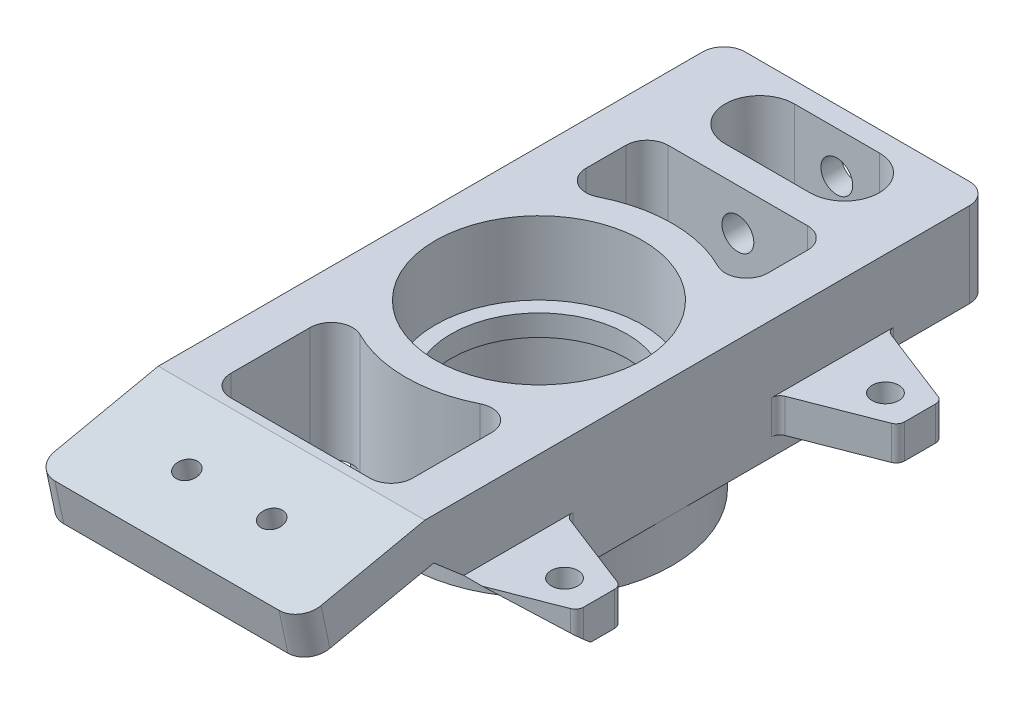
SolidWorks part; units mm, degrees
material "6061-T6 (SS)"
ref_plane "Front Plane" through (0, 0, 0) normal (0, 0, 1) x (1, 0, 0)
ref_plane "Top Plane" through (0, 0, 0) normal (0, 1, 0) x (1, 0, 0)
ref_plane "Right Plane" through (0, 0, 0) normal (1, 0, 0) x (0, 0, -1)
sketch "Geometry" plane through (0, 0, 0) normal (1, 0, 0) x (0, 0, -1)
  line L0 (0, 0) -> (0, -97.4059) construction
  line L1 (0, 0) -> (-30.7529, 0) construction
  line L2 (0, 22) -> (-45.5659, 22) construction
  dimension "D1" = 22
sketch "Sketch1" plane through (0, 0, 0) normal (0, 0, 1) x (1, 0, 0)
  line L1 (0, 0) -> (0, -13.28) construction
  line L3 (-30.9994, -10.5425) -> (-30.9994, -32.3865)
  line L4 (-30.9994, -32.3865) -> (-26.289, -32.3865)
  line L5 (-26.289, -32.3865) -> (-26.289, -38.7365)
  line L6 (-26.289, -38.7365) -> (-30.9994, -38.7365)
  line L7 (-30.9994, -38.7365) -> (-30.9994, -63.1205)
  line L8 (-30.9994, -63.1205) -> (-32.258, -63.1205)
  line L9 (-32.258, -63.1205) -> (-32.258, -59.3105)
  line L10 (-32.258, -59.3105) -> (-39.878, -59.3105)
  line L11 (-39.878, -59.3105) -> (-39.878, -10.5425)
  line L12 (-39.878, -10.5425) -> (-30.9994, -10.5425)
  line L13 (-80.1186, -10.5425) -> (80.1186, -10.5425) construction
  dimension "D1" = 6.35
  dimension "D2" = 21.844
  dimension "D3" = 24.384
  dimension "D4" = 52.578
  dimension "D5" = 61.9989
  dimension "D6" = 64.516
  dimension "D7" = 79.756
  dimension "D8" = 48.768
revolve "Bearing Housing" add sketch "Sketch1" angle 360 about L1
fillet "Bearing Fillet" radius 6.35 1 edges at (-32.258, -59.3105, 0)
sketch "Sketch2" plane through (0, -10.5425, 0) normal (0, -1, 0) x (-1, 0, 0)
  line L0 (-39.878, 50.8) -> (-39.878, 0)
  line L1 (39.878, 50.8) -> (39.878, 0)
  line L2 (-39.878, 50.8) -> (39.878, 50.8)
  circle A0 centre (0, 0) radius 39.878 construction
  arc A1 (-39.878, 0) -> (39.878, 0) centre (0, 0) cw
  dimension "D1" = 50.8
extrude "LBJ Prep" add sketch "Sketch2" along normal blind 35.56
sketch "Sketch3" plane through (-39.878, 0, 0) normal (-1, 0, 0) x (0, 0, 1)
  line L0 (-50.8, -10.5425) -> (-95.1865, -10.5425)
  line L1 (-95.1865, -10.5425) -> (-95.1865, -35.9425)
  line L2 (-95.1865, -35.9425) -> (-58.42, -35.9425)
  line L3 (-58.42, -35.9425) -> (-50.8, -46.1025)
  line L4 (-50.8, -46.1025) -> (-50.8, -10.5425)
  circle A1 centre (-78.74, -23.2425) radius 10.3505 construction
  dimension "D3" = 25.4
  dimension "D4" = 20.701
  dimension "D2" = 7.62
  dimension "D1" = 78.74
  dimension "D5" = 12.7
  dimension "D6" = 6.096
extrude "LBJ Extrude" add sketch "Sketch3" against normal up to surface (79.756 mm away) up to face at (39.878, -28.3225, -25.4)
sketch "Sketch4" plane through (0, -35.9425, 0) normal (0, -1, 0) x (1, 0, 0)
  line L0 (-12.7, -78.74) -> (12.7, -78.74) construction
  line L1 (0, -200000) -> (0, 200052.2037) construction
  line L2 (-12.7, -68.3895) -> (12.7, -68.3895)
  line L3 (-12.7, -89.0905) -> (12.7, -89.0905)
  arc A0 (-12.7, -68.3895) -> (-12.7, -89.0905) centre (-12.7, -78.74) ccw
  arc A1 (12.7, -89.0905) -> (12.7, -68.3895) centre (12.7, -78.74) ccw
  point P4 (0, -78.74)
  dimension "D1" = 20.701
  dimension "D2" = 78.74
  dimension "D3" = 25.4
extrude "LBJ Slot" cut sketch "Sketch4" against normal through all
sketch "Sketch8" plane through (0, -46.1025, 0) normal (0, -1, 0) x (1, 0, 0)
  line L0 (-27.178, -29.1824) -> (-27.178, -59.4995)
  line L1 (-27.178, -59.4995) -> (27.178, -59.4995)
  line L2 (27.178, -59.4995) -> (27.178, -29.1824)
  line L3 (-39.878, 0) -> (-39.878, -50.8) construction
  line L4 (39.878, -50.8) -> (39.878, 0) construction
  line L5 (12.7, -68.3895) -> (-12.7, -68.3895) construction
  arc A0 (-39.878, 0) -> (39.878, 0) centre (0, 0) ccw construction
  arc A1 (-27.178, -29.1824) -> (27.178, -29.1824) centre (0, 0) ccw
  dimension "D1" = 12.7
  dimension "D2" = 12.7
  dimension "D3" = 8.89
extrude "LBJ Weight Saivng" cut sketch "Sketch8" against normal up to surface (35.56 mm away)
fillet "LBJ Fillet" radius 6.35 4 edges at (-27.178, -23.2425, -59.4995) (27.178, -23.2425, -59.4995) (27.178, -28.3225, -29.1824) (-27.178, -28.3225, -29.1824)
sketch "Sketch12" plane through (0, 0, -95.1865) normal (0, 0, -1) x (-1, 0, 0)
  line L0 (0, 200000) -> (0, -200097.4059) construction
  circle A0 centre (0, -22.958) radius 4.7625
  dimension "D1" = 9.525
  dimension "D2" = 22.958
extrude "LBJ Hole" cut sketch "Sketch12" against normal up to surface (35.687 mm away) up to face at (0, -23.2425, -59.4995)
sketch "Alignment for LBJ Clearance" plane through (0, 0, -95.1865) normal (0, 0, -1) x (-1, 0, 0)
  line L0 (0, -22.958) -> (8.6177, -33.2282) construction
  line L1 (0, 200000) -> (0, -200097.4059) construction
  circle A1 centre (0, -22.958) radius 12.7 construction
  circle A2 centre (0, -22.958) radius 4.7625 construction
  dimension "D1" = 25.4
  dimension "D2" = 40
ref_plane "Plane1" through (0, -22.958, -95.1865) normal (-0.6428, -0.766, 0) x (-0.766, 0.6428, 0)
sketch "Sketch17" plane through (0, -22.958, -95.1865) normal (-0.6428, -0.766, 0) x (-0.766, 0.6428, 0)
  line L0 (0, -6.096) -> (0, -26.797) construction
  line L1 (4.7625, -26.797) -> (-4.7625, -26.797) construction
  line L3 (-4.7625, -6.096) -> (4.7625, -6.096) construction
  line L7 (4.7625, -26.797) -> (-4.7625, -26.797) construction
  line L8 (-1.27, -16.4465) -> (1.27, -16.4465) construction
  line L9 (-1.27, -6.096) -> (1.27, -6.096)
  line L10 (-1.27, -26.797) -> (1.27, -26.797)
  arc A2 (-1.27, -6.096) -> (-1.27, -26.797) centre (-1.27, -16.4465) ccw
  arc A3 (1.27, -26.797) -> (1.27, -6.096) centre (1.27, -16.4465) ccw
  point P7 (0, -16.4465)
  dimension "D1" = 2.54
  dimension "D2" = 20.701
extrude "LBJ Widening" cut sketch "Sketch17" along normal through all
mirror "LBJ Widening " about plane through (0, 0, 0) normal (1, 0, 0) of "LBJ Widening"
sketch "Sketch5" plane through (0, -10.5425, 0) normal (0, -1, 0) x (-1, 0, 0)
  line L0 (-39.878, -44.45) -> (39.878, -44.45)
  line L1 (39.878, -44.45) -> (39.878, 0)
  line L2 (-39.878, -44.45) -> (-39.878, 0)
  circle A0 centre (0, 0) radius 39.878 construction
  arc A1 (-39.878, 0) -> (39.878, 0) centre (0, 0) ccw
  dimension "D1" = 44.45
extrude "UBJ Area Prep" add sketch "Sketch5" along normal blind 35.56
sketch "UBJ Angle " plane through (-39.878, 0, 0) normal (-1, 0, 0) x (0, 0, 1)
  line L0 (44.45, -10.5425) -> (73.9986, -10.5425)
  line L1 (73.9986, -10.5425) -> (111.266, -18.4639)
  line L2 (111.266, -18.4639) -> (108.6256, -30.8864)
  line L3 (108.6256, -30.8864) -> (71.3581, -22.965)
  line L4 (71.3581, -22.965) -> (44.45, -46.1025)
  line L5 (44.45, -46.1025) -> (44.45, -10.5425)
  line L6 (92.6323, -14.5032) -> (69.5361, -123.1622) construction
  line L7 (71.3581, -22.965) -> (73.9986, -10.5425) construction
  line L8 (0, 0) -> (79.4354, 0) construction
  line L9 (44.45, -10.5425) -> (-95.1865, -10.5425) construction
  line L10 (-27.2547, 22) -> (21.0785, 22) construction
  line L11 (0, 0) -> (0, 33.0044) construction
  circle A0 centre (84.7344, -51.66) radius 10.3251 construction
  dimension "D8" = 20.6502
  dimension "D1" = 19.05
  dimension "D2" = 38.1
  dimension "D3" = 12.7
  dimension "D5" = 22
  dimension "D7" = 12
  dimension "D4" = 84.7344
  dimension "D6" = 73.66
extrude "UBJ Angle Mount" add sketch "UBJ Angle " against normal up to surface (79.756 mm away) up to face at (39.878, -33.0396, -30.099)
sketch "Sketch7" plane through (0, -7.4603, -1.5857) normal (0, -0.9781, -0.2079) x (1, 0, 0)
  line L0 (0, 112.6735) -> (0, 78.6798) construction
  line L2 (-12.7, 93.6235) -> (12.7, 93.6235) construction
  line L3 (39.878, 112.6735) -> (-39.878, 112.6735) construction
  circle A2 centre (-12.7, 93.6235) radius 3.2639
  circle A3 centre (12.7, 93.6235) radius 3.2639
  point P3 (0, 93.6235)
  dimension "D4" = 6.5278
  dimension "D1" = 25.4
  dimension "D2" = 19.05
extrude "Camber Block Holes" cut sketch "Sketch7" against normal up to surface (12.7 mm away) up to face at (0, -14.5032, 92.6323)
sketch "Sketch9" plane through (0, -46.1025, 0) normal (0, -1, 0) x (1, 0, 0)
  line L0 (-27.178, 29.1824) -> (-27.178, 71.3581)
  line L1 (-27.178, 71.3581) -> (27.178, 71.3581)
  line L2 (27.178, 71.3581) -> (27.178, 29.1824)
  line L4 (-39.878, 44.45) -> (-39.878, 0) construction
  line L5 (39.878, 0) -> (39.878, 44.45) construction
  line L6 (39.878, 71.3581) -> (-39.878, 71.3581) construction
  arc A3 (-27.178, 29.1824) -> (27.178, 29.1824) centre (0, 0) cw
  arc A4 (39.878, 0) -> (-39.878, 0) centre (0, 0) ccw construction
  dimension "D1" = 12.7
  dimension "D2" = 12.7
extrude "UBJ Weight Saving" cut sketch "Sketch9" against normal up to surface (35.56 mm away)
fillet "UBJ Fillets" radius 6.35 4 edges at (27.178, -28.3225, 29.1824) (-27.178, -28.3225, 29.1824) (27.178, -16.7537, 71.3581) (-27.178, -16.7537, 71.3581)
ref_plane "Brake Caliper Face " through (0, -30.7025, 0) normal (0, 1, 0) x (1, 0, 0)
sketch "Sketch13" plane through (0, -30.7025, 0) normal (0, 1, 0) x (1, 0, 0)
  line L0 (55.6468, 116.3651) -> (55.6468, 49.0638) construction
  line L1 (0, 0) -> (78.791, 0) construction
  line L2 (65.9968, -54.35) -> (65.9968, -41.65)
  line L3 (65.9968, -41.65) -> (39.878, -31.49)
  line L4 (39.878, -31.49) -> (39.878, -64.51)
  line L5 (39.878, -64.51) -> (65.9968, -54.35)
  line L6 (39.878, 95.1865) -> (39.878, -73.9986) construction
  line L7 (65.9968, -48) -> (55.6468, -48) construction
  line L8 (39.878, 31.49) -> (39.878, 64.51)
  line L9 (39.878, 64.51) -> (65.9968, 54.35)
  line L10 (65.9968, 54.35) -> (65.9968, 41.65)
  line L11 (65.9968, 41.65) -> (39.878, 31.49)
  circle A0 centre (55.6468, -48) radius 4
  circle A1 centre (55.6468, 48) radius 4
  dimension "D3" = 8
  dimension "D1" = 55.6468
  dimension "D2" = 96
  dimension "D4" = 6.35
  dimension "D5" = 33.02
  dimension "D6" = 12.7
extrude "Brake Arms" add sketch "Sketch13" against normal blind 10.16
sketch "Sketch15" plane through (39.878, 0, 0) normal (-1, 0, 0) x (0, 0, 1)
  line L0 (64.51, -28.8535) -> (50.5439, -40.8625)
  line L1 (44.45, -46.1025) -> (71.3581, -22.965) construction
  line L2 (50.5439, -40.8625) -> (64.51, -40.8625)
  line L3 (50.5439, -40.8625) -> (64.51, -40.8625) construction
  line L4 (64.51, -28.8535) -> (64.51, -40.8625)
  line L5 (64.51, -40.8625) -> (64.51, -30.7025) construction
extrude "Upper Brake Cut" cut sketch "Sketch15" against normal through all
sketch "Sketch16" plane through (39.878, 0, 0) normal (-1, 0, 0) x (0, 0, 1)
  line L0 (-58.42, -35.9425) -> (-95.1865, -35.9425)
  line L1 (-95.1865, -35.9425) -> (-58.42, -35.9425) construction
  line L2 (-95.1865, -35.9425) -> (-95.1865, -46.1025)
  line L3 (-95.1865, -46.1025) -> (-50.8, -46.1025)
  line L4 (-50.8, -46.1025) -> (-58.42, -35.9425)
  line L5 (-95.1865, -10.5425) -> (-95.1865, -35.9425) construction
extrude "Lower Brake Cut" cut sketch "Sketch16" against normal through all
fillet "Fillet1" radius 2.54 7 edges at (65.9968, -34.1461, 54.35) (65.9968, -35.7825, 41.65) (65.9968, -35.7825, -41.65) (65.9968, -35.7825, -54.35) (39.878, -33.3225, -64.51) (39.878, -35.7825, -31.49) (39.878, -35.7825, 31.49)
sketch "Sketch14" plane through (-39.878, 0, 0) normal (-1, 0, 0) x (0, 0, 1)
  line L0 (73.9986, -10.5425) -> (-95.1865, -10.5425) construction
  circle A0 centre (-31.242, -20.1945) radius 3.175
  circle A1 centre (-31.242, -37.4665) radius 3.175
  circle A2 centre (-55.118, -20.1945) radius 3.175
  dimension "D3" = 6.35
  dimension "D4" = 6.35
  dimension "D5" = 6.35
  dimension "D1" = 17.272
  dimension "D2" = 23.876
  dimension "D6" = 31.242
  dimension "D7" = 9.652
extrude "Tie Rod Mound" cut sketch "Sketch14" against normal blind 6.35
fillet "Fillet2" radius 6.35 4 edges at (-39.878, -23.2425, -95.1865) (39.878, -23.2425, -95.1865) (39.878, -24.6752, 109.9458) (-39.878, -24.6752, 109.9458)
equation "\"Wheel_Offset\"= 22mm"
equation "\"HUB_to_UBJ_Lat\"= 2.9in"
equation "\"Hub_to_UBJ_Vert\"= 3.336in"
equation "\"Hub_to_LBJ_Lat\"= 1.77in"
equation "\"Hub_to_LBJ_Vert\"= 3.1in"
equation "\"Wheel_face_to_Upright_back\"= 1.2812in'This is the distance between the whee face to the upright back."
equation "\"D2@Sketch4\"=\"Hub_to_LBJ_Vert\""
equation "\"D5@UBJ Angle \" = \"Wheel_Offset\""
equation "\"UBJ_Angle\"= 12deg"
equation "\"D7@UBJ Angle \" = \"UBJ_Angle\""
equation "\"D4@UBJ Angle \"=\"Hub_to_UBJ_Vert\""
equation "\"D6@UBJ Angle \"=\"HUB_to_UBJ_Lat\""
equation "\"D1@Geometry\" = \"Wheel_Offset\""
equation "\"D2@Sketch12\"=\"Hub_to_LBJ_Lat\"-\"Wheel_Offset\""
equation "\"D1@Sketch3\"=\"Hub_to_LBJ_Vert\""
equation "\"D1@Sketch7\"=\"Hub_to_LBJ_Lat\""
